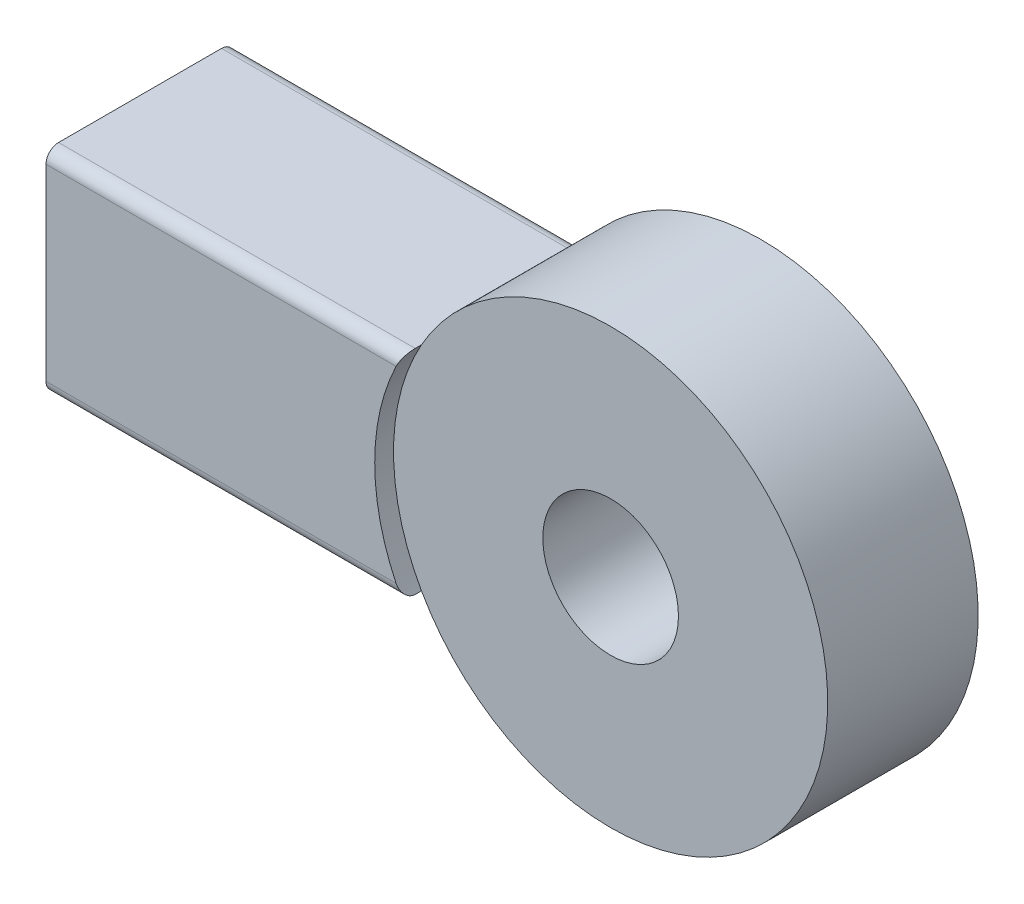
SolidWorks part; units mm, degrees
ref_plane "Front" through (0, 0, 0) normal (0, 0, 1) x (1, 0, 0)
ref_plane "Top" through (0, 0, 0) normal (0, 1, 0) x (1, 0, 0)
ref_plane "Right" through (0, 0, 0) normal (1, 0, 0) x (0, 0, -1)
sketch "Sketch1" plane through (0, 0, 0) normal (0, 0, 1) x (1, 0, 0)
  line L0 (0, 0) -> (-29.3153, 0) construction
  line L1 (-15.0905, -8.4982) -> (-43.54, -8.4982)
  line L3 (-15.0905, 8.4982) -> (-43.54, 8.4982)
  line L4 (-43.54, -8.4982) -> (-43.54, 8.4982)
  line L5 (-15.0905, -8.4982) -> (-43.54, 8.4982) construction
  line L6 (-15.0905, 8.4982) -> (-43.54, -8.4982) construction
  circle A0 centre (0, 0) radius 17.3189
  circle A1 centre (0, 0) radius 5.4117
  arc A2 (-6.8887, 15.8899) -> (16.7579, 4.3722) centre (0, 0) ccw construction
  circle A3 centre (0, 0) radius 5.4117 construction
  point P3 (-29.3153, 0)
extrude "Boss-Extrude1" add sketch "Sketch1" along normal mid plane 12 contours A0 region at (-16.829, 0, 0)
extrude "Boss-Extrude2" add sketch "Sketch1<3>" along normal mid plane 15 contours A0 L3 L4 L1 region at (-30.0601, 0, 0)
sketch "Sketch1<3>" plane through (0, 0, 0) normal (0, 0, 1) x (1, 0, 0) same geometry as "Sketch1"
sketch "Sketch2" plane through (-43.54, 0, 0) normal (-1, 0, 0) x (0, 0, 1)
  line L8 (-5.5, 6.4982) -> (-5.5, -6.4982)
  line L9 (-5.5, -6.4982) -> (5.5, -6.4982)
  line L10 (5.5, -6.4982) -> (5.5, 6.4982)
  line L11 (5.5, 6.4982) -> (-5.5, 6.4982)
  line L12 (-5.5, 6.4982) -> (-5.5, -6.4982)
  line L13 (-5.5, -6.4982) -> (5.5, -6.4982)
  line L14 (5.5, -6.4982) -> (5.5, 6.4982)
  line L15 (5.5, 6.4982) -> (-5.5, 6.4982)
  dimension "D1" = 2
extrude "Cut-Extrude1" cut sketch "Sketch2" against normal blind 26
fillet "Fillet1" radius 1 4 edges at (-29.3153, 8.4982, -7.5) (-29.3153, -8.4982, -7.5) (-29.3153, 8.4982, 7.5) (-29.3153, -8.4982, 7.5)
